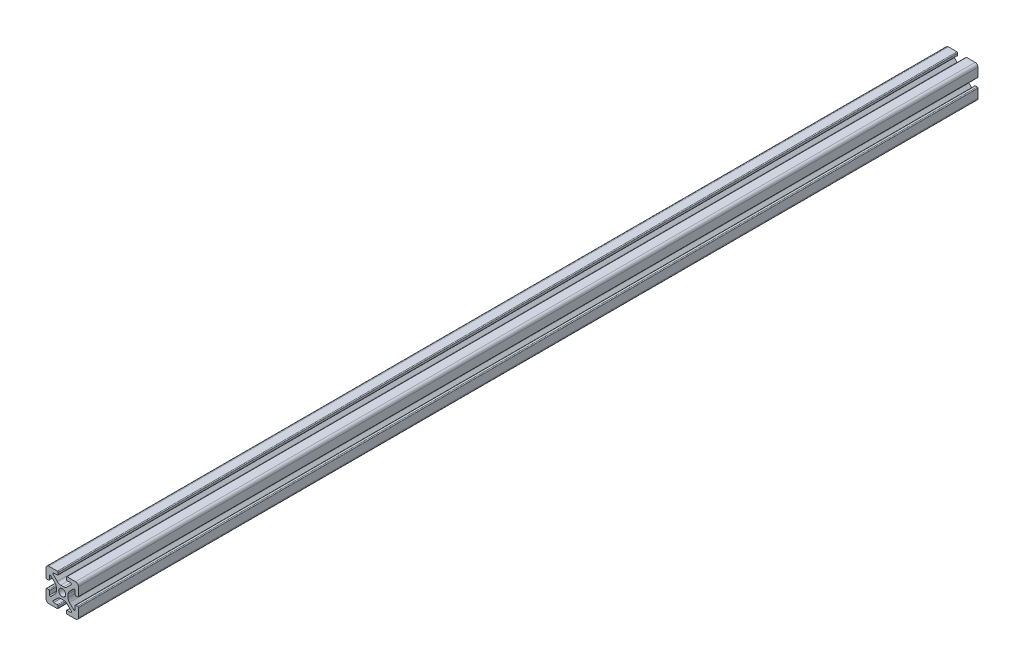
SolidWorks part; units mm, degrees
ref_plane "Front Plane" through (0, 0, 0) normal (0, 0, 1) x (1, 0, 0)
ref_plane "Top Plane" through (0, 0, 0) normal (0, 1, 0) x (1, 0, 0)
ref_plane "Right Plane" through (0, 0, 0) normal (1, 0, 0) x (0, 0, -1)
sketch "Sketch2" plane through (0, 0, 0) normal (0, 0, 1) x (1, 0, 0)
  line L0 (0, 10) -> (0, -10) construction
  line L1 (-10, 0) -> (10, 0) construction
  line L2 (2.5, -10) -> (10, -10)
  line L3 (10, -10) -> (10, -2.5)
  line L4 (2.5, -10) -> (2.5, -7.9246)
  line L5 (2.5, -7.9246) -> (6.4571, -7.9246)
  line L6 (6.4571, -7.9246) -> (2.1325, -3.6)
  line L7 (0, 0) -> (10, -10) construction
  line L8 (10, -2.5) -> (7.9246, -2.5)
  line L9 (7.9246, -2.5) -> (7.9246, -6.4571)
  line L10 (7.9246, -6.4571) -> (3.6, -2.1325)
  line L11 (5.7623, -4.2948) -> (4.2948, -5.7623) construction
  circle A0 centre (0, 0) radius 2.15
  arc A1 (5.25, -7.9246) -> (5.6036, -7.0711) centre (5.25, -7.4246) ccw construction
  point P8 (0, -3.6)
  point P16 (5.0286, -5.0286)
  dimension "Center Hole Diameter" = 4.3
  dimension "D3" = 0.5
  dimension "Rail Height" = 20
  dimension "Rail Width" = 20
  dimension "T-Slot Width" = 5
  dimension "Slot Depth" = 6.4
  dimension "Slot Inner Width" = 11.5
sketch "Sketch3" plane through (0, 0, 0) normal (1, 0, 0) x (0, 0, -1)
  line L0 (-152.4, -10) -> (152.4, -10) construction
  line L1 (-127, 0) -> (127, 0) construction
  line L2 (0, 10) -> (0, -10) construction
  line L3 (0, 10) -> (0, -10) construction
  point P6 (-127, 0)
  point P8 (127, 0)
  dimension "Length" = 304.8
  dimension "D1" = 25.4
sketch "Sketch4" plane through (0, 0, 0) normal (0, 0, 1) x (1, 0, 0)
  line L0 (3, -10) -> (8.25, -10)
  line L1 (2.5, -10) -> (10, -10) construction
  line L2 (2.5, -10) -> (2.5, -7.9246) construction
  line L3 (2.5, -7.9246) -> (6.4571, -7.9246) construction
  line L4 (2.5, -8.4246) -> (2.5, -9.5)
  line L5 (3, -7.9246) -> (5.25, -7.9246)
  line L6 (0, -3.6) -> (0.8898, -3.6)
  line L7 (6.4571, -7.9246) -> (2.1325, -3.6) construction
  line L8 (3.0112, -4.4787) -> (5.6036, -7.0711)
  line L9 (10, -10) -> (10, -2.5) construction
  line L10 (7.9246, -6.4571) -> (3.6, -2.1325) construction
  line L11 (7.9246, -2.5) -> (7.9246, -6.4571) construction
  line L12 (7.9246, -5.25) -> (7.9246, -3)
  line L13 (10, -2.5) -> (7.9246, -2.5) construction
  line L14 (8.4246, -2.5) -> (9.5, -2.5)
  line L15 (10, -3) -> (10, -8.25)
  line L16 (7.0711, -5.6036) -> (4.4787, -3.0112)
  line L17 (3.6, 0) -> (3.6, -0.8898)
  line L18 (-10, 0) -> (10, 0) construction
  line L19 (0, -3.6) -> (0, -2.15)
  line L20 (0, 10) -> (0, -10) construction
  line L21 (3.6, 0) -> (2.15, 0)
  arc A0 (2.5, -9.5) -> (3, -10) centre (3, -9.5) ccw
  arc A1 (5.25, -7.9246) -> (5.6036, -7.0711) centre (5.25, -7.4246) ccw construction
  arc A2 (2.5, -8.4246) -> (3, -7.9246) centre (3, -8.4246) cw
  arc A3 (5.25, -7.9246) -> (5.6036, -7.0711) centre (5.25, -7.4246) ccw
  arc A4 (0.8898, -3.6) -> (3.0112, -4.4787) centre (0.8898, -6.6) cw
  arc A5 (8.25, -10) -> (10, -8.25) centre (8.25, -8.25) ccw
  arc A6 (7.0711, -5.6036) -> (7.9246, -5.25) centre (7.4246, -5.25) ccw
  arc A7 (7.9246, -3) -> (8.4246, -2.5) centre (8.4246, -3) cw
  arc A8 (9.5, -2.5) -> (10, -3) centre (9.5, -3) cw
  arc A9 (4.4787, -3.0112) -> (3.6, -0.8898) centre (6.6, -0.8898) cw
  circle A10 centre (0, 0) radius 2.15 construction
  arc A11 (0, -2.15) -> (2.15, 0) centre (0, 0) ccw
  dimension "D1" = 1.75
  dimension "D2" = 3
extrude "Boss-Extrude1" add sketch "Sketch4" along normal mid plane 555
mirror "Mirror1" about plane through (0, 0, 0) normal (1, 0, 0) of bodies 134
mirror "Mirror2" about plane through (0, 0, 0) normal (0, 1, 0) of bodies 135
equation "\"D3@Sketch2\"=\"T-Slot Width@Sketch2\"*0.1"
equation "\"D1@Sketch4\"=\"D3@Sketch2\"*3.5"
equation "\"D2@Sketch4\"=\"D3@Sketch2\"*6"
equation "\"D1@Boss-Extrude1\"=\"Length@Sketch3\""
